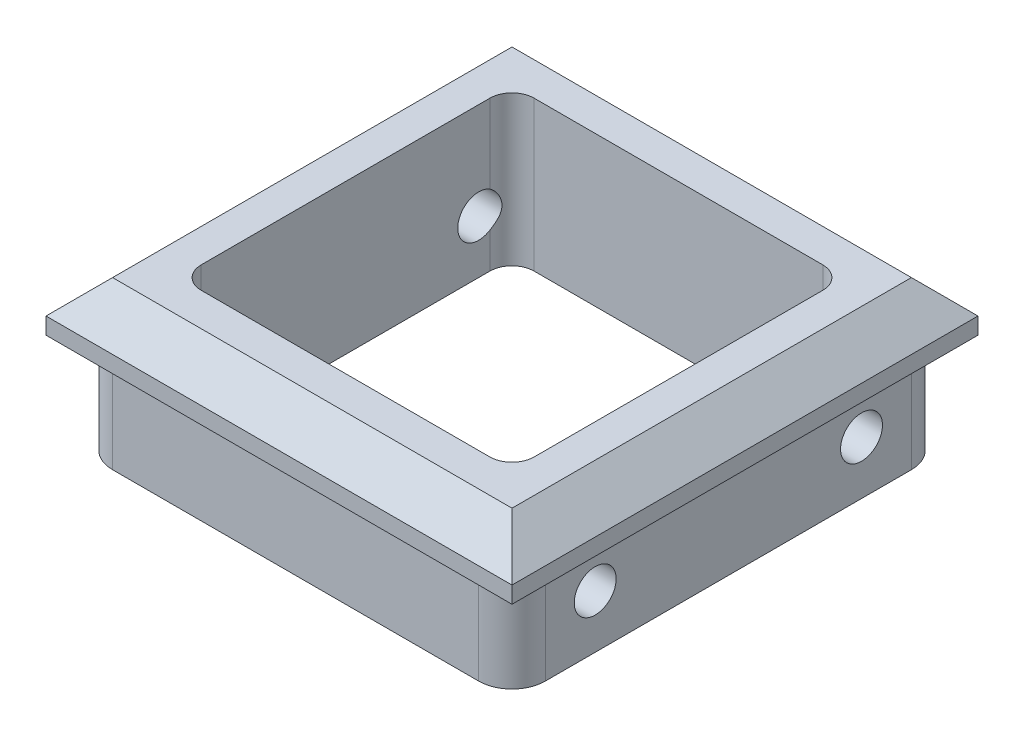
SolidWorks part; units mm, degrees
material "Delrin 2700 NC010, Low Viscosity Acetal Copolymer (SS)"
ref_plane "Front Plane" through (0, 0, 0) normal (0, 0, 1) x (1, 0, 0)
ref_plane "Top Plane" through (0, 0, 0) normal (0, 1, 0) x (1, 0, 0)
ref_plane "Right Plane" through (0, 0, 0) normal (1, 0, 0) x (0, 0, -1)
sketch "Sketch1" plane through (0, 0, 0) normal (0, 1, 0) x (1, 0, 0)
  line L1 (41.275, 41.275) -> (-41.275, 41.275)
  line L2 (41.275, 41.275) -> (41.275, -41.275)
  line L3 (41.275, -41.275) -> (-41.275, -41.275)
  line L4 (-41.275, 41.275) -> (-41.275, -41.275)
  line L5 (41.275, 41.275) -> (-41.275, -41.275) construction
  line L6 (41.275, -41.275) -> (-41.275, 41.275) construction
  line L7 (44.45, 44.45) -> (-44.45, 44.45)
  line L8 (44.45, 44.45) -> (44.45, -44.45)
  line L9 (44.45, -44.45) -> (-44.45, -44.45)
  line L10 (-44.45, 44.45) -> (-44.45, -44.45)
  line L11 (44.45, 44.45) -> (-44.45, -44.45) construction
  line L12 (44.45, -44.45) -> (-44.45, 44.45) construction
  line L13 (27.5336, 31.75) -> (-27.5336, 31.75)
  line L14 (31.75, 27.5336) -> (31.75, -27.5336)
  line L15 (27.5336, -31.75) -> (-27.5336, -31.75)
  line L16 (-31.75, 27.5336) -> (-31.75, -27.5336)
  line L17 (31.75, 31.75) -> (-31.75, -31.75) construction
  line L18 (31.75, -31.75) -> (-31.75, 31.75) construction
  arc A0 (-27.5336, -31.75) -> (-31.75, -27.5336) centre (-27.5336, -27.5336) cw
  arc A1 (31.75, -27.5336) -> (27.5336, -31.75) centre (27.5336, -27.5336) cw
  arc A2 (27.5336, 31.75) -> (31.75, 27.5336) centre (27.5336, 27.5336) cw
  arc A3 (-27.5336, 31.75) -> (-31.75, 27.5336) centre (-27.5336, 27.5336) ccw
  point P0 (0, 0)
  point P6 (0, 0)
  point P11 (0, 0)
  dimension "D4" = 4.2164
  dimension "D1" = 88.9
  dimension "D2" = 3.175
  dimension "D3" = 63.5
extrude "Boss-Extrude1" add sketch "Sketch1" along normal blind 19.05 contours L1 L4 L3 L2 A3 L13 A2 L14 A1 L15 A0 L16 region at (40.1076, 0, 0)
extrude "Boss-Extrude2" add sketch "Sketch1<3>" along normal blind 9.525 from surface contours L1 L4 L3 L2 A3 L13 A2 L14 A1 L15 A0 L16 | L7 L10 L9 L8 L4 L1 L2 L3 region at (40.1076, 0, 0) region at (43.1928, 0, 0) starting at face at (0, 19.05, 0)
sketch "Sketch1<3>" plane through (0, 0, 0) normal (0, 1, 0) x (1, 0, 0) same geometry as "Sketch1"
fillet "Fillet1" radius 6.35 4 edges at (41.275, 9.525, 41.275) (-41.275, 9.525, -41.275) (41.275, 9.525, -41.275) (-41.275, 9.525, 41.275)
chamfer "Chamfer1" distance 6.35 angle 45 4 edges at (44.45, 28.575, 0) (0, 28.575, -44.45) (0, 28.575, 44.45) (-44.45, 28.575, 0)
sketch "Sketch2" plane through (-41.275, 0, 0) normal (-1, 0, 0) x (0, 0, 1)
  line L0 (-25.4, 10.16) -> (25.4, 10.16) construction
  circle A2 centre (-25.4, 10.16) radius 4
  circle A3 centre (25.4, 10.16) radius 4
  point P1 (0, 10.16)
  dimension "D1" = 10.16
  dimension "D2" = 8
  dimension "D3" = 50.8
extrude "Cut-Extrude2" cut sketch "Sketch2" against normal through all
